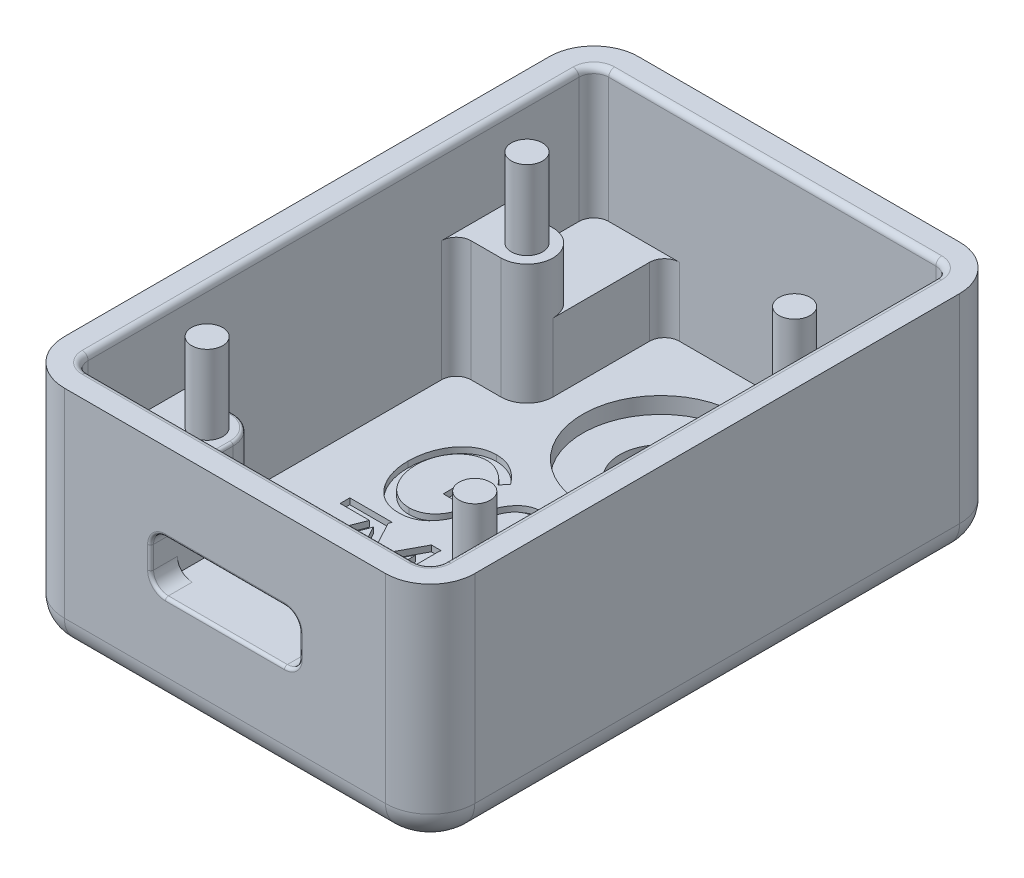
SolidWorks part; units mm, degrees
material "ABS PC"
ref_plane "Front" through (0, 0, 0) normal (0, 0, 1) x (1, 0, 0)
ref_plane "Top" through (0, 0, 0) normal (0, 1, 0) x (1, 0, 0)
ref_plane "Right" through (0, 0, 0) normal (1, 0, 0) x (0, 0, -1)
sketch "草图1" plane through (0, 0, 0) normal (0, 1, 0) x (1, 0, 0)
  line L0 (-9, 10.755) -> (9, -10.755) construction
  line L1 (-12, 18.255) -> (-12, -16.755)
  line L2 (-12, -16.755) -> (12, -16.755)
  line L3 (12, -16.755) -> (12, 18.255)
  line L4 (12, 18.255) -> (-12, 18.255)
  line L5 (-9, 12.505) -> (-11, 12.505)
  line L6 (-9, 9.005) -> (-11, 9.005)
  line L7 (9, 12.505) -> (11, 12.505)
  line L8 (9, 9.005) -> (11, 9.005)
  line L9 (-9, -9.005) -> (-11, -9.005)
  line L10 (9, -9.005) -> (11, -9.005)
  line L11 (-12, -13.755) -> (-5, -13.755)
  line L12 (-5, -13.755) -> (-5, -16.755)
  line L13 (12, -13.755) -> (5, -13.755)
  line L14 (5, -13.755) -> (5, -16.755)
  line L15 (-7.25, -10.755) -> (-7.25, -12.755)
  line L16 (7.25, -10.755) -> (7.25, -12.755)
  line L17 (-13.8, 20.055) -> (-13.8, -18.555)
  line L18 (-13.8, -18.555) -> (13.8, -18.555)
  line L19 (13.8, -18.555) -> (13.8, 20.055)
  line L20 (13.8, 20.055) -> (-13.8, 20.055)
  line L21 (9, -9.005) -> (-9, -9.005)
  circle A0 centre (-9, 10.755) radius 1.05
  circle A1 centre (-9, -10.755) radius 1.05
  circle A2 centre (9, -10.755) radius 1.05
  circle A3 centre (9, 10.755) radius 1.05
  circle A4 centre (-9, 10.755) radius 1.75
  circle A5 centre (9, 10.755) radius 1.75
  circle A6 centre (9, -10.755) radius 1.75
  circle A7 centre (-9, -10.755) radius 1.75
  arc A8 (-11, 9.005) -> (-12, 8.005) centre (-11, 8.005) ccw
  arc A9 (-11, 12.505) -> (-12, 13.505) centre (-11, 13.505) cw
  arc A10 (11, 9.005) -> (12, 8.005) centre (11, 8.005) cw
  arc A11 (11, 12.505) -> (12, 13.505) centre (11, 13.505) ccw
  arc A12 (11, -9.005) -> (12, -8.005) centre (11, -8.005) ccw
  arc A13 (-11, -9.005) -> (-12, -8.005) centre (-11, -8.005) cw
  arc A14 (-7.25, -12.755) -> (-6.25, -13.755) centre (-6.25, -12.755) ccw
  arc A15 (7.25, -12.755) -> (6.25, -13.755) centre (6.25, -12.755) cw
  arc A16 (-12, 17.255) -> (-11, 18.255) centre (-11, 17.255) cw
  arc A17 (11, 18.255) -> (12, 17.255) centre (11, 17.255) cw
  arc A18 (-12, -15.755) -> (-11, -16.755) centre (-11, -15.755) ccw
  arc A19 (12, -15.755) -> (11, -16.755) centre (11, -15.755) cw
  point P9 (0, 0)
  point P47 (0, -16.755)
  dimension "D1" = 2.1
  dimension "D4" = 3.5
  dimension "D9" = 1
  dimension "D10" = 3
  dimension "D13" = 1.8
  dimension "D2" = 18
  dimension "D3" = 21.51
  dimension "D5" = 3
  dimension "D6" = 3
  dimension "D7" = 6
  dimension "D8" = 7.5
  dimension "D11" = 5
  dimension "D12" = 5
extrude "凸台-拉伸2" add sketch "草图1<3>" along normal blind 5.3 separate body contours L19 L20 L17 L18 L4 L3 L2 L1 | L1 A16 L4 | L4 A17 L3 | A18 L1 L2 | L3 A19 L2 | A1 | A2 | A0 | A3 region at (-11.7766, 0, -18.0316) region at (11.7766, 0, -18.0316) region at (-11.7766, 0, 16.5316) region at (11.7766, 0, 16.5316) region at (0, 0, -19.5804) region at (-9, 0, -10.755) region at (-9, 0, 10.755) region at (9, 0, 10.755) region at (9, 0, -10.755)
sketch "草图1<3>" plane through (0, 0, 0) normal (0, 1, 0) x (1, 0, 0) same geometry as "草图1"
extrude "凸台-拉伸3" add sketch "草图1" against normal blind 8.1 contours A14 L15 A7 L9 A13 L1 L11 | L12 L11 L1 L2 | L13 L14 L2 L3 | A7 A1 | L5 A9 L1 A8 L6 A4 | A0 A4 | A11 L7 A5 L8 A10 L3 | A5 A3 | L16 A15 L13 L3 A12 L10 A6 | A6 A2 | L19 L20 L17 L18 L4 L3 L2 L1 | L1 A16 L4 | L4 A17 L3 | L3 A19 L2 | A18 L1 L2 | A1 | A0 | A3 | A2 region at (-11.7766, 0, -18.0316) region at (-11.1849, 0, -10.755) region at (11.7766, 0, -18.0316) region at (-11.7646, 0, 8.7696) region at (-7.7976, 0, -11.9574) region at (11.1849, 0, -10.755) region at (-8.4662, 0, 15.2418) region at (-11.7766, 0, 16.5316) region at (-7.7976, 0, 9.5526) region at (11.9187, 0, 10.88) region at (10.2024, 0, -11.9574) region at (10.2024, 0, 9.5526) region at (8.4662, 0, 15.2418) region at (11.7766, 0, 16.5316) region at (0, 0, -19.5804) region at (-9, 0, -10.755) region at (-9, 0, 10.755) region at (9, 0, 10.755) region at (9, 0, -10.755)
extrude "凸台-拉伸4" add sketch "草图1<5>" against normal blind 4.6 from offset 3.5 contours A15 L16 L15 A14 L11 L12 L2 L14 L13 | L21 L0 A6 region at (8.0249, 0, 9.1298) region at (-0.0173, 0, 12.5172) offset against normal yes
sketch "草图1<5>" plane through (0, 0, 0) normal (0, 1, 0) x (1, 0, 0) same geometry as "草图1"
sketch "草图2" plane through (0, 0, 18.555) normal (0, 0, 1) x (1, 0, 0)
  line L0 (-5, -3.5) -> (-5, 0) construction
  line L1 (-5, -3.5) -> (-5, 0)
  line L2 (-5, -3.5) -> (5, -3.5) construction
  line L3 (-5, -3.5) -> (5, -3.5)
  line L4 (5, -3.5) -> (5, 0) construction
  line L5 (5, -3.5) -> (5, 0)
  line L6 (5, 0) -> (-5, 0)
  line L7 (5, -1.75) -> (-5, -1.75) construction
  line L8 (0, 0) -> (0, -3.5) construction
  arc A0 (4, -3.5) -> (5, -2.5) centre (4, -2.5) ccw
  arc A1 (4, 0) -> (5, -1) centre (4, -1) cw
  arc A2 (-4, -3.5) -> (-5, -2.5) centre (-4, -2.5) cw
  arc A3 (-4, 0) -> (-5, -1) centre (-4, -1) ccw
  dimension "D1" = 1
extrude "切除-拉伸1" cut sketch "草图2" against normal blind 2.3 contours L3 A0 L5 L6 L1 region at (0, -1.75, 18.555)
extrude "凸台-拉伸5" add sketch "草图1<6>" against normal blind 2 from offset 8.1 contours A4 L0 L21 L10 A12 L3 A10 L8 A5 L7 A11 A17 L4 A16 L1 A9 L5 | L0 A4 L6 A8 L1 A13 L9 L21 | L1 A16 L4 | L19 L20 L17 L18 L4 L3 L2 L1 | L4 A17 L3 | L5 A9 L1 A8 L6 A4 | A0 A4 | A11 L7 A5 L8 A10 L3 | A5 A3 | L0 L21 A7 L15 A14 L11 L12 L2 L14 L13 A15 L16 A6 | L12 L11 L1 L2 | A14 L15 A7 L9 A13 L1 L11 | A7 A1 | L16 A15 L13 L3 A12 L10 A6 | L13 L14 L2 L3 | L21 L0 A6 | A6 A2 | A18 L1 L2 | L3 A19 L2 | A1 | A2 | A0 | A3 region at (-8.4195, 0, -9.1567) region at (2.7659, 0, -7.6078) region at (-5.2011, 0, 1.8777) region at (-9.9244, 0, -11.1868) region at (8.0249, 0, 9.1298) region at (-0.0173, 0, 12.5172) region at (-11.1849, 0, -10.755) region at (9.4318, 0, 9.8306) region at (8.4195, 0, 9.1567) region at (10, 0, 9.0863) region at (-10.2949, 0, 12.0499) region at (-7.7976, 0, 9.5526) region at (8.4662, 0, 15.2418) region at (11.1849, 0, -10.755) region at (-8.4662, 0, 15.2418) region at (-11.7766, 0, -18.0316) region at (11.7766, 0, 16.5316) region at (-11.7766, 0, 16.5316) region at (11.7766, 0, -18.0316) region at (7.2995, 0, -10.755) region at (0, 0, -19.5804) region at (-9, 0, 10.755) region at (9, 0, -10.755) offset against normal yes
sketch "草图1<6>" plane through (0, 0, 0) normal (0, 1, 0) x (1, 0, 0) same geometry as "草图1"
sketch "草图3" plane through (0, -8.1, 0) normal (0, 1, 0) x (1, 0, 0)
  line L0 (-11, 18.255) -> (-6.25, 18.255)
  line L2 (-9, 12.505) -> (-11, 12.505) construction
  line L3 (-9, 12.505) -> (-11, 12.505)
  line L4 (-12, 17.255) -> (-12, 13.505) construction
  line L5 (-12, 17.255) -> (-12, 13.505)
  line L6 (6.25, 18.255) -> (11, 18.255)
  line L7 (7.25, 17.255) -> (7.25, 10.755)
  line L8 (12, 13.505) -> (12, 17.255) construction
  line L9 (12, 13.505) -> (12, 17.255)
  line L10 (9, 12.505) -> (11, 12.505) construction
  line L11 (9, 12.505) -> (11, 12.505)
  line L14 (-7.25, 17.255) -> (-7.25, 10.755)
  line L15 (-7.25, 10.755) -> (7.25, 10.755) construction
  line L16 (0, 18.255) -> (0, 10.755) construction
  line L17 (11, 18.255) -> (-11, 18.255) construction
  arc A0 (-9, 9.005) -> (-9, 12.505) centre (-9, 10.755) ccw construction
  arc A1 (-9, 9.005) -> (-9, 12.505) centre (-9, 10.755) ccw
  arc A2 (-12, 13.505) -> (-11, 12.505) centre (-11, 13.505) ccw construction
  arc A3 (-12, 13.505) -> (-11, 12.505) centre (-11, 13.505) ccw
  arc A4 (-11, 18.255) -> (-12, 17.255) centre (-11, 17.255) ccw construction
  arc A5 (-11, 18.255) -> (-12, 17.255) centre (-11, 17.255) ccw
  arc A6 (9, 12.505) -> (9, 9.005) centre (9, 10.755) ccw construction
  arc A7 (9, 12.505) -> (9, 9.005) centre (9, 10.755) ccw
  arc A8 (12, 17.255) -> (11, 18.255) centre (11, 17.255) ccw construction
  arc A9 (12, 17.255) -> (11, 18.255) centre (11, 17.255) ccw
  arc A10 (11, 12.505) -> (12, 13.505) centre (11, 13.505) ccw construction
  arc A11 (11, 12.505) -> (12, 13.505) centre (11, 13.505) ccw
  arc A12 (-6.25, 18.255) -> (-7.25, 17.255) centre (-6.25, 17.255) ccw
  arc A13 (6.25, 18.255) -> (7.25, 17.255) centre (6.25, 17.255) cw
  circle A14 centre (0, 10.755) radius 2.75
  circle A15 centre (0, 10.755) radius 5.25
  line M2 (9, 12.505) -> (11, 12.505)
  arc M3 (11, 12.505) -> (12, 13.505) centre (11, 13.505) ccw
  line M4 (12, 13.505) -> (12, 17.255)
  arc M5 (12, 17.255) -> (11, 18.255) centre (11, 17.255) ccw
  line M6 (11, 18.255) -> (-11, 18.255)
  arc M7 (-11, 18.255) -> (-12, 17.255) centre (-11, 17.255) ccw
  line M8 (-12, 17.255) -> (-12, 13.505)
  arc M9 (-12, 13.505) -> (-11, 12.505) centre (-11, 13.505) ccw
  line M10 (-11, 12.505) -> (-9, 12.505)
  arc M11 (-9, 12.505) -> (-9, 9.005) centre (-9, 10.755) cw
  arc M21 (9, 9.005) -> (9, 12.505) centre (9, 10.755) cw
  dimension "D1" = 1
  dimension "D2" = 1
  dimension "D3" = 10.5
  dimension "D4" = 5.5
extrude "凸台-拉伸6" add sketch "草图3" along normal blind 4.6 contours A12 L14 M6 M7 M8 M9 M10 M11 | A13 L7 M6 M21 M2 M3 M4 M5 region at (9.5247, -8.1, -15.3232) region at (-9.5247, -8.1, -15.3232)
fillet "圆角1" radius 3 4 edges at (-13.8, -2.4, -20.055) (13.8, -2.4, -20.055) (13.8, -2.4, 18.555) (-13.8, -2.4, 18.555)
fillet "圆角2" radius 0.2 24 edges at (5, 0, 15.255) (-11.7071, 0, 8.7121) (-10, 0, 9.005) (-7.7626, 0, 9.5176) (-7.25, 0, 11.755) (-5.625, 0, 13.755) (11.7071, 0, 8.7121) (10, 0, 9.005) (7.7626, 0, 9.5176) (7.25, 0, 11.755) (6.9571, 0, 13.4621) (5, -1.75, 18.555) (0, -3.5, 18.555) (-5, -1.75, 18.555) (0, 0, 18.555) (-5, -1.75, 13.755) (-6.9571, 0, 13.4621) (-5, 0, 15.255) (5, -1.75, 13.755) (5.625, 0, 13.755) (4.7071, -3.2071, 18.555) (4.7071, -0.2929, 18.555) (-4.7071, -3.2071, 18.555) (-4.7071, -0.2929, 18.555)
fillet "圆角3" radius 2 8 edges at (12.9213, -10.1, 17.6763) (0, -10.1, 18.555) (-12.9213, -10.1, 17.6763) (-13.8, -10.1, -0.75) (-12.9213, -10.1, -19.1763) (0, -10.1, -20.055) (12.9213, -10.1, -19.1763) (13.8, -10.1, -0.75)
extrude "切除-拉伸2" cut sketch "草图3<7>" against normal blind 3 contours A14 region at (0, -8.1, -10.755)
sketch "草图3<7>" plane through (0, -8.1, 0) normal (0, 1, 0) x (1, 0, 0) same geometry as "草图3"
extrude "切除-拉伸3" cut sketch "草图3<8>" against normal blind 1.1 contours A15 A14 region at (-5.1015, -8.1, -10.755)
sketch "草图3<8>" plane through (0, -8.1, 0) normal (0, 1, 0) x (1, 0, 0) same geometry as "草图3"
fillet "圆角4" radius 0.4 1 edges at (0, -10.1, -8.005)
fillet "圆角5" radius 0.4 8 edges at (-11.7071, 5.3, -17.9621) (0, 5.3, -18.255) (11.7071, 5.3, -17.9621) (12, 5.3, -0.75) (11.7071, 5.3, 16.4621) (0, 5.3, 16.755) (-11.7071, 5.3, 16.4621) (-12, 5.3, -0.75)
sketch "草图4" plane through (0, -8.1, 0) normal (0, 1, 0) x (1, 0, 0)
  text T0 "GaAs" font "Century Gothic" height 6.35
extrude "切除-拉伸4" cut sketch "草图4" against normal blind 0.4
sketch "草图5" plane through (0, -8.1, 0) normal (0, 1, 0) x (1, 0, 0)
  text T0 "ZYH" font "Century Gothic" height 6.35
extrude "切除-拉伸5" cut sketch "草图5" against normal blind 0.4
